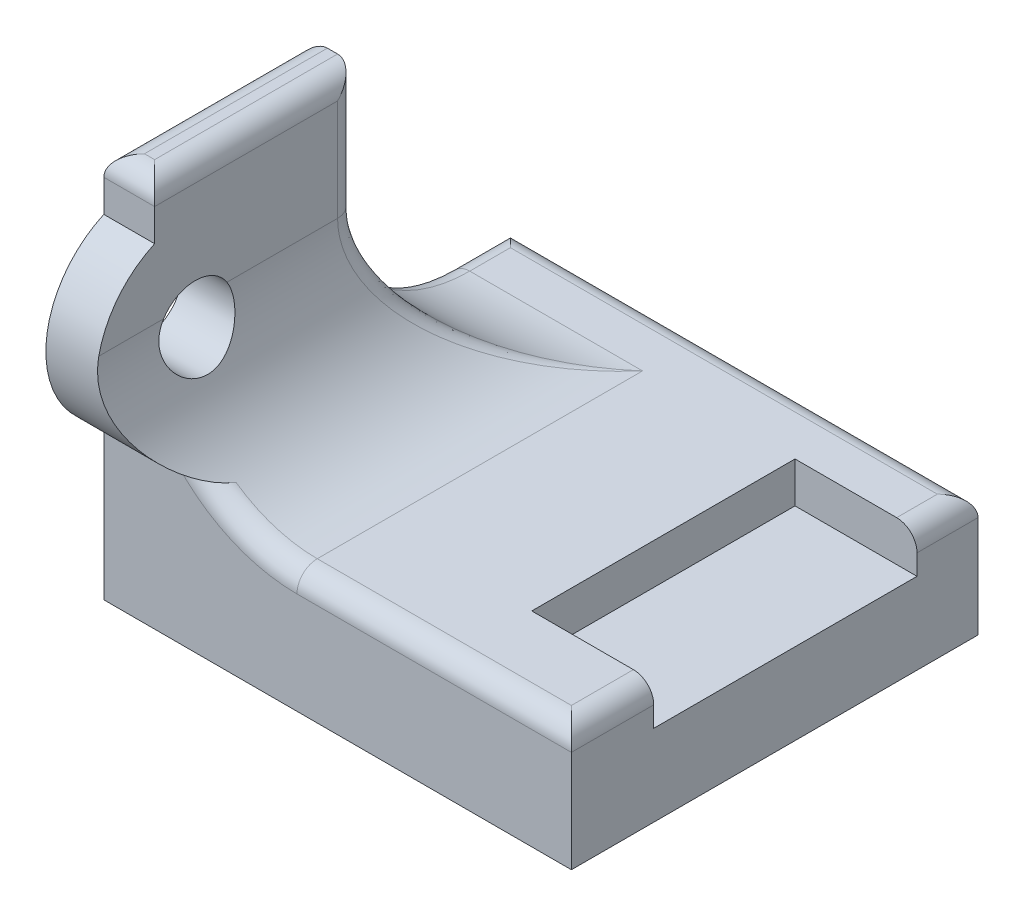
SolidWorks part; units mm, degrees
ref_plane "Alzado" through (0, 0, 0) normal (0, 0, 1) x (1, 0, 0)
ref_plane "Planta" through (0, 0, 0) normal (0, 1, 0) x (1, 0, 0)
ref_plane "Vista lateral" through (0, 0, 0) normal (1, 0, 0) x (0, 0, -1)
sketch "Croquis1" plane through (0, 0, 0) normal (0, 1, 0) x (1, 0, 0)
  line L1 (0, 0) -> (23, 0)
  line L2 (0, 0) -> (0, -20)
  line L3 (0, -20) -> (23, -20)
  line L4 (23, 0) -> (23, -20)
  dimension "D1" = 23
  dimension "D2" = 20
extrude "Saliente-Extruir1" add sketch "Croquis1" along normal blind 9
sketch "Croquis2" plane through (0, 9, 0) normal (0, 1, 0) x (1, 0, 0)
  line L0 (23, -20) -> (23, 0) construction
  line L1 (23, -15.95) -> (17, -15.95)
  line L3 (17, -3) -> (23, -3)
  line L4 (17, -15.95) -> (17, -3)
  line L7 (23, -3) -> (23, -15.95)
  point P0 (23, -10)
  dimension "D1" = 6
  dimension "D2" = 12.95
extrude "Cortar-Extruir1" cut sketch "Croquis2" against normal blind 2
sketch "Croquis3" plane through (0, 9, 0) normal (0, 1, 0) x (1, 0, 0)
  line L0 (0, -20) -> (23, -20) construction
  line L1 (0, 0) -> (2.5, 0)
  line L2 (0, 0) -> (0, -20)
  line L3 (0, -20) -> (2.5, -20)
  line L4 (2.5, 0) -> (2.5, -20)
  dimension "D1" = 2.5
extrude "Saliente-Extruir3" add sketch "Croquis3" along normal blind 15
sketch "Croquis4" plane through (2.5, 0, 0) normal (1, 0, 0) x (0, 0, -1)
  line L0 (-20, 9) -> (0, 9) construction
  line L1 (-20, 24) -> (-20, 9) construction
  circle A0 centre (-18, 15) radius 1.85
  point P6 (-20, 16.5)
  dimension "D1" = 3.7
  dimension "D2" = 6
  dimension "D3" = 2
extrude "Cortar-Extruir4" cut sketch "Croquis4" against normal up to vertex (2.5 mm away) up to point (0, 24, 20)
sketch "Croquis6" plane through (2.5, 0, 0) normal (1, 0, 0) x (0, 0, -1)
  line L0 (-20, 24) -> (-20, 9) construction
  line L1 (-20, 19.4184) -> (-20, 10.5816)
  arc A2 (-20, 19.4184) -> (-20, 10.5816) centre (-18, 15) ccw
extrude "Saliente-Extruir7" add sketch "Croquis6" against normal up to vertex (2.5 mm away) up to point (0, 24, 20)
sketch "Croquis7" plane through (2.5, 0, 0) normal (1, 0, 0) x (0, 0, -1)
  line L0 (-20, 9) -> (0, 9) construction
  line L1 (0, 24) -> (-10, 24)
  line L2 (0, 24) -> (0, 9)
  line L3 (0, 9) -> (-10, 9)
  line L4 (-10, 24) -> (-10, 9)
extrude "Cortar-Extruir5" cut sketch "Croquis7" against normal up to vertex (2.5 mm away) up to point (0, 24, 0)
sketch "Croquis8" plane through (0, 0, 0) normal (0, -1, 0) x (1, 0, 0)
  line L4 (0, 20) -> (0, 0)
  line L5 (0, 0) -> (23, 0)
  line L6 (23, 0) -> (23, 20)
  line L7 (23, 20) -> (0, 20)
  line L8 (0, 20) -> (0, 0)
  line L9 (0, 0) -> (23, 0)
  line L10 (23, 0) -> (23, 20)
  line L11 (23, 20) -> (0, 20)
  dimension "D1" = 0
extrude "Cortar-Extruir6" cut sketch "Croquis8" against normal blind 3
sketch "Croquis9" plane through (0, 24, 0) normal (0, 1, 0) x (1, 0, 0)
  line L4 (2.5, -10) -> (0, -10)
  line L5 (0, -10) -> (0, -20)
  line L6 (0, -20) -> (2.5, -20)
  line L7 (2.5, -20) -> (2.5, -10)
  line L8 (2.5, -10) -> (0, -10)
  line L9 (0, -10) -> (0, -20)
  line L10 (0, -20) -> (2.5, -20)
  line L11 (2.5, -20) -> (2.5, -10)
  dimension "D1" = 0
extrude "Cortar-Extruir7" cut sketch "Croquis9" against normal blind 2
fillet "Redondeo1" radius 7 2 edges at (1.25, 9, 10)
fillet "Redondeo2" radius 1 13 edges at (4.5503, 11.0503, 7.9497) (0, 19, 10) (0, 11.0503, 7.9497) (7.1472, 9.4072, 20) (1.25, 22, 20) (0, 22, 15) (2.5, 22, 15) (2.5, 19, 10) (23, 9, 1.5) (23, 9, 17.975) (0, 9, 1.5)
